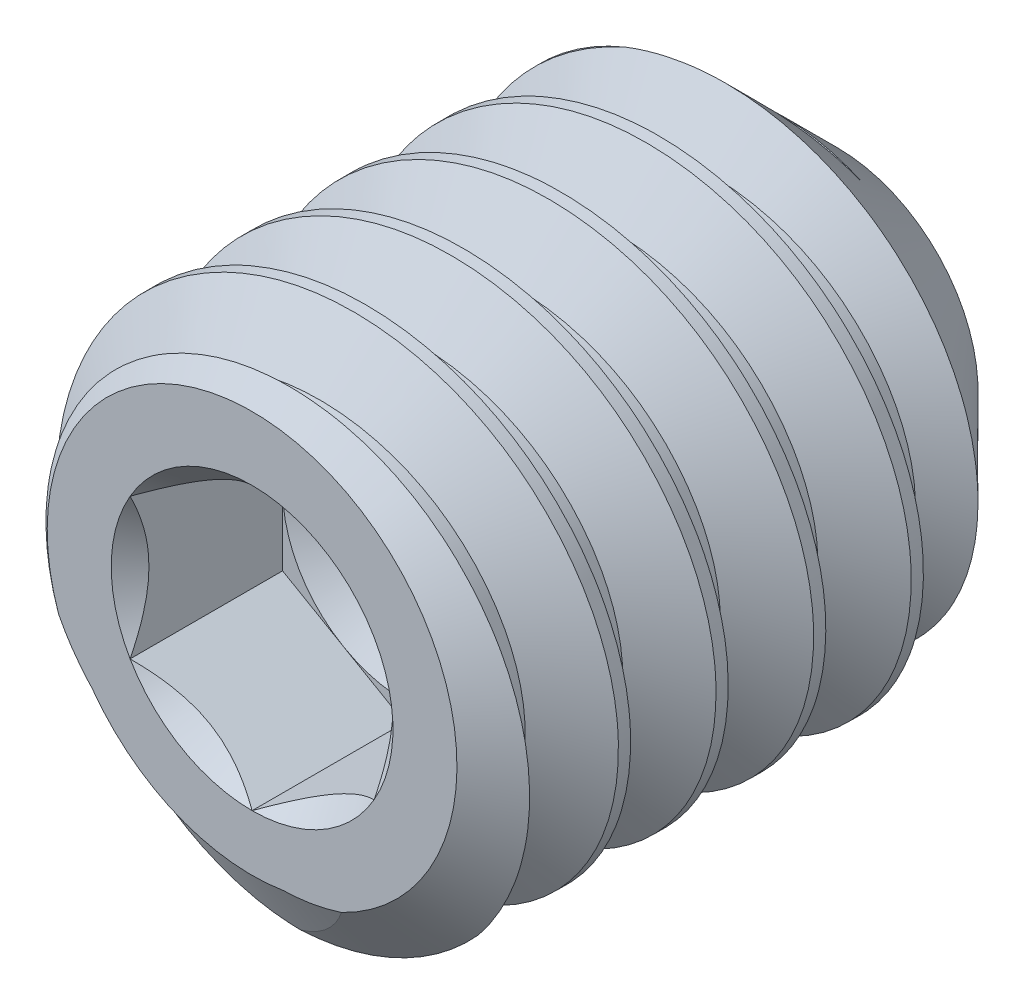
SolidWorks part; units mm, degrees
material "AISI 304"
ref_plane "Front" through (0, 0, 0) normal (0, 0, 1) x (1, 0, 0)
ref_plane "Top" through (0, 0, 0) normal (0, 1, 0) x (1, 0, 0)
ref_plane "Right" through (0, 0, 0) normal (1, 0, 0) x (0, 0, -1)
sketch "Sketch22" plane through (0, 0, 0) normal (1, 0, 0) x (0, 0, -1)
  line L0 (-2.0384, 0) -> (-2.0384, 1.6662)
  line L1 (-2.0384, 1.6662) -> (-1.7467, 2.0828)
  line L2 (-1.7467, 2.0828) -> (1.7826, 2.0828)
  line L3 (1.7826, 2.0828) -> (2.7241, 1.1413)
  line L4 (2.7241, 1.1413) -> (2.0384, 0)
  line L5 (2.0384, 0) -> (-2.0384, 0)
  line L6 (2.0384, 0) -> (2.7241, 0) construction
  line L7 (2.7241, 0) -> (2.7241, 1.1413) construction
  line L8 (2.7241, -1.1413) -> (2.0384, 0) construction
  line L9 (-1.7467, -2.0828) -> (1.7826, -2.0828) construction
  dimension "Dia" = 4.1656
  dimension "Length" = 4.7625
  dimension "D3" = 35
  dimension "D5" = 118
  dimension "D6" = 45
  dimension "D7" = 3.3325
revolve "Revolve1" add sketch "Sketch22" angle 360 about L6
ref_plane "Plane1" through (0, 0, -2.7241) normal (0, 0, 1) x (1, 0, 0)
sketch "Sketch27" plane through (0, 0, -2.7241) normal (0, 0, 1) x (1, 0, 0)
  circle A0 centre (0, 0) radius 2.0828 construction
  circle A1 centre (0, 0) radius 2.0828
curve "Helix/Spiral1" pitch 0.7937 height 5.8103 radius 2.0828 centre (0, 0, -2.7241) axis (0, 0, 1) start towards (0, 1, 0)
sketch "Sketch28" plane through (0, 0, 0) normal (1, 0, 0) x (0, 0, -1)
  line L0 (2.7241, 2.0828) -> (3.4187, 2.0828)
  line L1 (3.4187, 2.0828) -> (3.1409, 1.6016)
  line L2 (3.1409, 1.6016) -> (3.0019, 1.6016)
  line L3 (3.0019, 1.6016) -> (2.7241, 2.0828)
  line L4 (2.863, 1.8422) -> (3.2798, 1.8422) construction
  line L6 (-1.7467, 2.0828) -> (1.7826, 2.0828) construction
  line L7 (2.7241, 2.3089) -> (2.7241, -2.3089) construction
  dimension "D1" = 0.1389
  dimension "D3" = 60
  dimension "D2" = 0.6945
sweep "Cut-Sweep2" cut profiles "Sketch28" path "Helix/Spiral1" align with end faces yes
sketch "Sketch23" plane through (0, 0, 2.0384) normal (0, 0, 1) x (1, 0, 0)
  line L1 (0, 1.1457) -> (-0.9922, 0.5728)
  line L2 (-0.9922, 0.5728) -> (-0.9922, -0.5728)
  line L3 (-0.9922, -0.5728) -> (0, -1.1457)
  line L4 (0, -1.1457) -> (0.9922, -0.5728)
  line L5 (0.9922, -0.5728) -> (0.9922, 0.5728)
  line L6 (0.9922, 0.5728) -> (0, 1.1457)
  circle A0 centre (0, 0) radius 0.9922 construction
  dimension "Hex" = 1.9844
extrude "Cut-Extrude10" cut sketch "Sketch23" against normal blind 1.2402
sketch "Sketch24" plane through (0, 0, 2.0384) normal (0, 0, 1) x (1, 0, 0)
  circle A0 centre (0, 0) radius 1.1457
extrude "Cut-Extrude11" cut sketch "Sketch24" against normal through all draft 45
sketch "Sketch26" plane through (0, 0, 0.7981) normal (0, 0, 1) x (1, 0, 0)
  circle A0 centre (0, 0) radius 0.9922 construction
  circle A1 centre (0, 0) radius 0.9922
extrude "Cut-Extrude12" cut sketch "Sketch26" against normal through all draft 60
sketch "Sketch30" plane through (0, 0, 0) normal (1, 0, 0) x (0, 0, -1)
  line L0 (-1.7467, 2.0828) -> (1.7826, 2.0828) construction
  line L1 (-2.0384, 0) -> (-2.0384, 1.6662) construction
  line L2 (2.7241, 0) -> (2.7241, 1.1413) construction
  line L3 (-1.7467, -2.0828) -> (1.7826, -2.0828) construction
  point P0 (-2.0384, 2.0828)
  point P1 (2.7241, 2.0828)
  point P2 (2.7241, -2.0828)
  point P11 (0.7398, -2.0828)
  dimension "D1" = 1.9844
sketch "Sketch31" plane through (0, 0, 0) normal (1, 0, 0) x (0, 0, -1)
  line L2 (2.0384, 0) -> (2.7241, -1.1413)
  line L3 (2.7241, 1.1413) -> (2.0384, 0)
ref_plane "Plane2" through (0, 0, -2.7241) normal (0, 0, -1) x (-1, 0, 0)
ref_axis "Axis1" through (0, 0, -4.2916) along (0, 0, 1)
equation "\"D7@Sketch22\"=\"Dia@Sketch22\"*.8"
equation "\"D1@Sketch28\" = \"D4@Helix/Spiral1\" * .175"
equation "\"D3@Helix/Spiral1\" = \"Length@Sketch22\" + \"D4@Helix/Spiral1\" + .01"
equation "\"D1@Sketch30\" = \"D4@Helix/Spiral1\" * 2.5"
equation "\"hex Depth@Cut-Extrude10\" = \"Hex@Sketch23\" * .625"
equation "\"D2@Sketch28\" = \"D4@Helix/Spiral1\" * .875"
